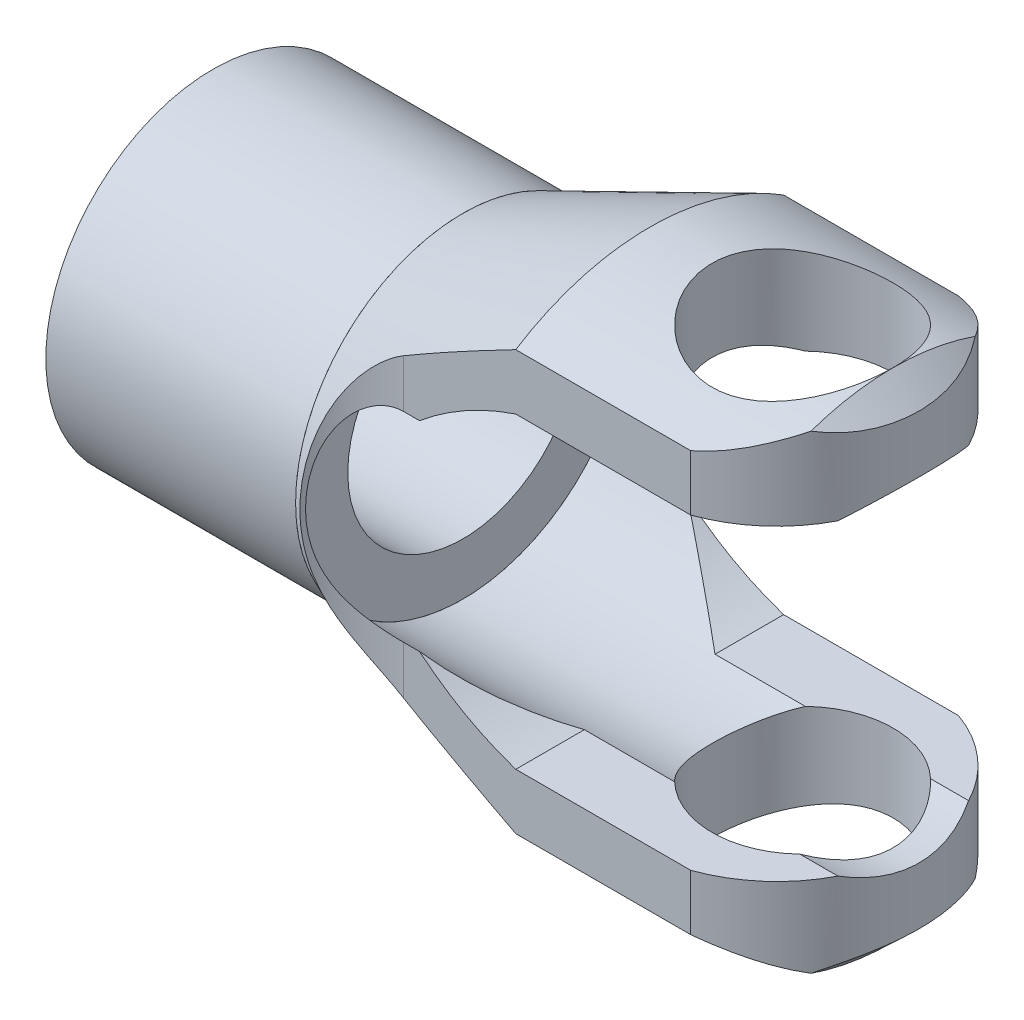
SolidWorks part; units mm, degrees
ref_plane "Front Plane" through (0, 0, 0) normal (0, 0, 1) x (1, 0, 0)
ref_plane "Top Plane" through (0, 0, 0) normal (0, 1, 0) x (1, 0, 0)
ref_plane "Right Plane" through (0, 0, 0) normal (1, 0, 0) x (0, 0, -1)
sketch "Sketch2" plane through (0, 0, 0) normal (1, 0, 0) x (0, 0, -1)
  circle A0 centre (0, 0) radius 13.85
extrude "Boss-Extrude1" add sketch "Sketch2" along normal blind 20.7
sketch "Sketch3" plane through (0, 0, 0) normal (1, 0, 0) x (0, 0, -1)
  circle A0 centre (0, 0) radius 9.525
extrude "Cut-Extrude1" cut sketch "Sketch3" along normal blind 30.7 contours A0
sketch "Sketch4" plane through (0, 0, 0) normal (0, 0, 1) x (1, 0, 0)
  line L0 (20.7, -13.85) -> (20.7, 13.85) construction
  line L1 (20.7, 13.85) -> (58.5486, 13.85)
  line L2 (20.7, 13.85) -> (20.7, 0)
  line L3 (0, 0) -> (58.5486, 0) construction
  line L5 (20.7, 13.85) -> (36.196, 20.6129)
  line L6 (36.196, 20.6129) -> (56.3665, 20.6129)
  line L7 (58.5486, 18.5628) -> (58.5486, 15.0336)
  line L8 (58.5486, 15.0336) -> (58.5486, 0)
  line L11 (58.5486, 18.5628) -> (56.3665, 20.6129)
revolve "Revolve1" add sketch "Sketch4" angle 360 about L3 region at (43.0031, 16.9081, 0)
sketch "Sketch5" plane through (0, 0, 0) normal (0, 0, 1) x (1, 0, 0)
  line L0 (0, 0) -> (58.5486, 0) construction
  line L1 (58.5486, -18.5628) -> (58.5486, 18.5628) construction
  line L2 (58.5486, 18.5628) -> (58.5486, -18.5628) construction
  line L3 (58.5486, 18.5628) -> (56.3665, 20.6129) construction
  line L4 (58.5486, 18.5628) -> (58.5486, 12.7478)
  line L5 (58.5486, 12.7478) -> (36.196, 12.7478)
  line L6 (36.196, 20.6129) -> (36.196, -20.6129) construction
  line L7 (20.7, 0) -> (25.7, 0)
  line L8 (20.7, 13.85) -> (20.7, -13.85) construction
  line L9 (25.7, -5.8341) -> (25.7, 5.8341)
  line L10 (58.5486, -12.7478) -> (36.196, -12.7478)
  line L11 (58.5486, 12.7478) -> (67.6641, 12.7478)
  line L12 (67.6641, 12.7478) -> (67.6641, -13.2143)
  line L13 (67.6641, -13.2143) -> (58.5486, -12.7478)
  arc A0 (36.196, 12.7478) -> (25.7, 5.8341) centre (43.9316, -10.42) ccw
  arc A1 (36.196, -12.7478) -> (25.7, -5.8341) centre (43.9316, 10.42) cw
extrude "Cut-Extrude2" cut sketch "Sketch5" against normal blind 30.7 and the other way blind 30.7 contours A1 L10 L13 L12 L11 L5 A0 L9 region at (47.7546, -0.0271, 0)
sketch "Sketch6" plane through (0, 0, 0) normal (0, 1, 0) x (1, 0, 0)
  line L0 (0, 0) -> (58.5486, 0) construction
  line L1 (58.5486, -13.4934) -> (58.5486, 13.4934) construction
  line L2 (36.196, -11.099) -> (36.196, 11.099)
  line L3 (36.196, -16.1984) -> (36.196, 16.1984) construction
  line L4 (36.196, 11.099) -> (50.696, 11.099)
  line L5 (36.196, -11.099) -> (50.696, -11.099)
  line L6 (36.196, 11.099) -> (26.8998, 11.099)
  line L7 (25.7, 16.0322) -> (20.7, 13.85) construction
  line L8 (36.196, -11.099) -> (26.8998, -11.099)
  line L9 (21.3327, 14.1261) -> (20.116, 21.3233)
  line L10 (20.116, 21.3233) -> (78.5664, 21.3233)
  line L11 (78.5664, 21.3233) -> (77.6648, -14.8889)
  line L12 (77.6648, -14.8889) -> (60.9862, -21.5003)
  line L13 (60.9862, -21.5003) -> (22.9709, -18.1946)
  line L14 (22.9709, -18.1946) -> (21.3327, -14.1261)
  arc A0 (50.696, 11.099) -> (50.696, -11.099) centre (46.7515, 0) cw
  arc A1 (26.8998, 11.099) -> (21.3327, 14.1261) centre (26.8998, 17.7317) cw
  arc A2 (26.8998, -11.099) -> (21.3327, -14.1261) centre (26.8998, -17.7317) ccw
  point P10 (36.196, 0)
extrude "Cut-Extrude3" cut sketch "Sketch6" against normal blind 30.7 and the other way blind 30.7 contours L8 A2 L14 L13 L12 L11 L10 L9 A1 L6 L4 A0 L5 region at (43.446, 0, 11.8236)
sketch "Sketch7" plane through (0, 0, 0) normal (0, 1, 0) x (1, 0, 0)
  circle A0 centre (48.8665, 0) radius 7.5
extrude "Cut-Extrude4" cut sketch "Sketch7" against normal blind 38 and the other way blind 33
